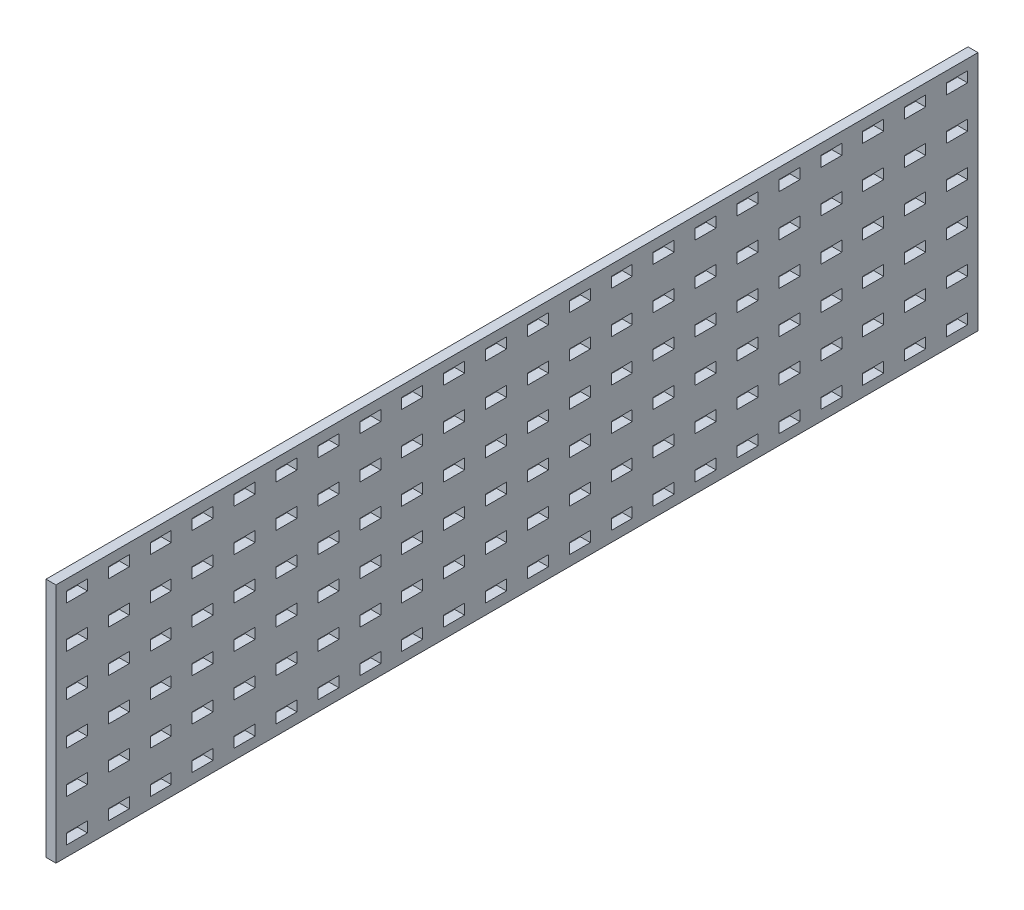
SolidWorks part; units mm, degrees
ref_plane "Front Plane" through (0, 0, 0) normal (0, 0, 1) x (1, 0, 0)
ref_plane "Top Plane" through (0, 0, 0) normal (0, 1, 0) x (1, 0, 0)
ref_plane "Right Plane" through (0, 0, 0) normal (1, 0, 0) x (0, 0, -1)
sketch "Sketch1" plane through (0, 0, 0) normal (1, 0, 0) x (0, 0, -1)
  line L1 (-279.4, -73.025) -> (279.4, -73.025)
  line L2 (-279.4, -73.025) -> (-279.4, 73.025)
  line L3 (-279.4, 73.025) -> (279.4, 73.025)
  line L4 (279.4, -73.025) -> (279.4, 73.025)
  line L5 (-279.4, -73.025) -> (279.4, 73.025) construction
  line L6 (-279.4, 73.025) -> (279.4, -73.025) construction
  point P0 (0, 0)
  dimension "D1" = 558.8
  dimension "D2" = 146.05
extrude "Boss-Extrude1" add sketch "Sketch1" along normal mid plane 6.0452
sketch "Sketch2" plane through (3.0226, 0, 0) normal (1, 0, 0) x (0, 0, -1)
  line L0 (-279.4, -73.025) -> (279.4, -73.025) construction
  line L1 (260.35, -60.325) -> (273.05, -60.325)
  line L2 (260.35, -60.325) -> (260.35, -66.675)
  line L3 (260.35, -66.675) -> (273.05, -66.675)
  line L4 (273.05, -60.325) -> (273.05, -66.675)
  line L5 (260.35, -60.325) -> (273.05, -66.675) construction
  line L6 (260.35, -66.675) -> (273.05, -60.325) construction
  line L7 (279.4, -73.025) -> (279.4, 73.025) construction
  line L8 (234.95, -66.675) -> (247.65, -66.675)
  line L9 (234.95, -60.325) -> (234.95, -66.675)
  line L10 (234.95, -60.325) -> (247.65, -60.325)
  line L11 (247.65, -60.325) -> (247.65, -66.675)
  line L12 (209.55, -66.675) -> (222.25, -66.675)
  line L13 (209.55, -60.325) -> (209.55, -66.675)
  line L14 (209.55, -60.325) -> (222.25, -60.325)
  line L15 (222.25, -60.325) -> (222.25, -66.675)
  line L16 (184.15, -66.675) -> (196.85, -66.675)
  line L17 (184.15, -60.325) -> (184.15, -66.675)
  line L18 (184.15, -60.325) -> (196.85, -60.325)
  line L19 (196.85, -60.325) -> (196.85, -66.675)
  line L20 (158.75, -66.675) -> (171.45, -66.675)
  line L21 (158.75, -60.325) -> (158.75, -66.675)
  line L22 (158.75, -60.325) -> (171.45, -60.325)
  line L23 (171.45, -60.325) -> (171.45, -66.675)
  line L24 (133.35, -66.675) -> (146.05, -66.675)
  line L25 (133.35, -60.325) -> (133.35, -66.675)
  line L26 (133.35, -60.325) -> (146.05, -60.325)
  line L27 (146.05, -60.325) -> (146.05, -66.675)
  line L28 (107.95, -66.675) -> (120.65, -66.675)
  line L29 (107.95, -60.325) -> (107.95, -66.675)
  line L30 (107.95, -60.325) -> (120.65, -60.325)
  line L31 (120.65, -60.325) -> (120.65, -66.675)
  line L32 (82.55, -66.675) -> (95.25, -66.675)
  line L33 (82.55, -60.325) -> (82.55, -66.675)
  line L34 (82.55, -60.325) -> (95.25, -60.325)
  line L35 (95.25, -60.325) -> (95.25, -66.675)
  line L36 (57.15, -66.675) -> (69.85, -66.675)
  line L37 (57.15, -60.325) -> (57.15, -66.675)
  line L38 (57.15, -60.325) -> (69.85, -60.325)
  line L39 (69.85, -60.325) -> (69.85, -66.675)
  line L40 (31.75, -66.675) -> (44.45, -66.675)
  line L41 (31.75, -60.325) -> (31.75, -66.675)
  line L42 (31.75, -60.325) -> (44.45, -60.325)
  line L43 (44.45, -60.325) -> (44.45, -66.675)
  line L44 (6.35, -66.675) -> (19.05, -66.675)
  line L45 (6.35, -60.325) -> (6.35, -66.675)
  line L46 (6.35, -60.325) -> (19.05, -60.325)
  line L47 (19.05, -60.325) -> (19.05, -66.675)
  line L48 (-19.05, -66.675) -> (-6.35, -66.675)
  line L49 (-19.05, -60.325) -> (-19.05, -66.675)
  line L50 (-19.05, -60.325) -> (-6.35, -60.325)
  line L51 (-6.35, -60.325) -> (-6.35, -66.675)
  line L52 (-44.45, -66.675) -> (-31.75, -66.675)
  line L53 (-44.45, -60.325) -> (-44.45, -66.675)
  line L54 (-44.45, -60.325) -> (-31.75, -60.325)
  line L55 (-31.75, -60.325) -> (-31.75, -66.675)
  line L56 (-69.85, -66.675) -> (-57.15, -66.675)
  line L57 (-69.85, -60.325) -> (-69.85, -66.675)
  line L58 (-69.85, -60.325) -> (-57.15, -60.325)
  line L59 (-57.15, -60.325) -> (-57.15, -66.675)
  line L60 (-95.25, -66.675) -> (-82.55, -66.675)
  line L61 (-95.25, -60.325) -> (-95.25, -66.675)
  line L62 (-95.25, -60.325) -> (-82.55, -60.325)
  line L63 (-82.55, -60.325) -> (-82.55, -66.675)
  line L64 (-120.65, -66.675) -> (-107.95, -66.675)
  line L65 (-120.65, -60.325) -> (-120.65, -66.675)
  line L66 (-120.65, -60.325) -> (-107.95, -60.325)
  line L67 (-107.95, -60.325) -> (-107.95, -66.675)
  line L68 (-146.05, -66.675) -> (-133.35, -66.675)
  line L69 (-146.05, -60.325) -> (-146.05, -66.675)
  line L70 (-146.05, -60.325) -> (-133.35, -60.325)
  line L71 (-133.35, -60.325) -> (-133.35, -66.675)
  line L72 (-171.45, -66.675) -> (-158.75, -66.675)
  line L73 (-171.45, -60.325) -> (-171.45, -66.675)
  line L74 (-171.45, -60.325) -> (-158.75, -60.325)
  line L75 (-158.75, -60.325) -> (-158.75, -66.675)
  line L76 (-196.85, -66.675) -> (-184.15, -66.675)
  line L77 (-196.85, -60.325) -> (-196.85, -66.675)
  line L78 (-196.85, -60.325) -> (-184.15, -60.325)
  line L79 (-184.15, -60.325) -> (-184.15, -66.675)
  line L80 (-222.25, -66.675) -> (-209.55, -66.675)
  line L81 (-222.25, -60.325) -> (-222.25, -66.675)
  line L82 (-222.25, -60.325) -> (-209.55, -60.325)
  line L83 (-209.55, -60.325) -> (-209.55, -66.675)
  line L84 (-247.65, -66.675) -> (-234.95, -66.675)
  line L85 (-247.65, -60.325) -> (-247.65, -66.675)
  line L86 (-247.65, -60.325) -> (-234.95, -60.325)
  line L87 (-234.95, -60.325) -> (-234.95, -66.675)
  line L88 (-273.05, -66.675) -> (-260.35, -66.675)
  line L89 (-273.05, -60.325) -> (-273.05, -66.675)
  line L90 (-273.05, -60.325) -> (-260.35, -60.325)
  line L91 (-260.35, -60.325) -> (-260.35, -66.675)
  line L92 (234.95, -41.275) -> (247.65, -41.275)
  line L93 (234.95, -34.925) -> (234.95, -41.275)
  line L94 (234.95, -34.925) -> (247.65, -34.925)
  line L95 (247.65, -34.925) -> (247.65, -41.275)
  line L96 (209.55, -41.275) -> (222.25, -41.275)
  line L97 (209.55, -34.925) -> (209.55, -41.275)
  line L98 (209.55, -34.925) -> (222.25, -34.925)
  line L99 (222.25, -34.925) -> (222.25, -41.275)
  line L100 (184.15, -41.275) -> (196.85, -41.275)
  line L101 (184.15, -34.925) -> (184.15, -41.275)
  line L102 (184.15, -34.925) -> (196.85, -34.925)
  line L103 (196.85, -34.925) -> (196.85, -41.275)
  line L104 (158.75, -41.275) -> (171.45, -41.275)
  line L105 (158.75, -34.925) -> (158.75, -41.275)
  line L106 (158.75, -34.925) -> (171.45, -34.925)
  line L107 (171.45, -34.925) -> (171.45, -41.275)
  line L108 (133.35, -41.275) -> (146.05, -41.275)
  line L109 (133.35, -34.925) -> (133.35, -41.275)
  line L110 (133.35, -34.925) -> (146.05, -34.925)
  line L111 (146.05, -34.925) -> (146.05, -41.275)
  line L112 (107.95, -41.275) -> (120.65, -41.275)
  line L113 (107.95, -34.925) -> (107.95, -41.275)
  line L114 (107.95, -34.925) -> (120.65, -34.925)
  line L115 (120.65, -34.925) -> (120.65, -41.275)
  line L116 (82.55, -41.275) -> (95.25, -41.275)
  line L117 (82.55, -34.925) -> (82.55, -41.275)
  line L118 (82.55, -34.925) -> (95.25, -34.925)
  line L119 (95.25, -34.925) -> (95.25, -41.275)
  line L120 (57.15, -41.275) -> (69.85, -41.275)
  line L121 (57.15, -34.925) -> (57.15, -41.275)
  line L122 (57.15, -34.925) -> (69.85, -34.925)
  line L123 (69.85, -34.925) -> (69.85, -41.275)
  line L124 (31.75, -41.275) -> (44.45, -41.275)
  line L125 (31.75, -34.925) -> (31.75, -41.275)
  line L126 (31.75, -34.925) -> (44.45, -34.925)
  line L127 (44.45, -34.925) -> (44.45, -41.275)
  line L128 (6.35, -41.275) -> (19.05, -41.275)
  line L129 (6.35, -34.925) -> (6.35, -41.275)
  line L130 (6.35, -34.925) -> (19.05, -34.925)
  line L131 (19.05, -34.925) -> (19.05, -41.275)
  line L132 (-19.05, -41.275) -> (-6.35, -41.275)
  line L133 (-19.05, -34.925) -> (-19.05, -41.275)
  line L134 (-19.05, -34.925) -> (-6.35, -34.925)
  line L135 (-6.35, -34.925) -> (-6.35, -41.275)
  line L136 (-44.45, -41.275) -> (-31.75, -41.275)
  line L137 (-44.45, -34.925) -> (-44.45, -41.275)
  line L138 (-44.45, -34.925) -> (-31.75, -34.925)
  line L139 (-31.75, -34.925) -> (-31.75, -41.275)
  line L140 (-69.85, -41.275) -> (-57.15, -41.275)
  line L141 (-69.85, -34.925) -> (-69.85, -41.275)
  line L142 (-69.85, -34.925) -> (-57.15, -34.925)
  line L143 (-57.15, -34.925) -> (-57.15, -41.275)
  line L144 (-95.25, -41.275) -> (-82.55, -41.275)
  line L145 (-95.25, -34.925) -> (-95.25, -41.275)
  line L146 (-95.25, -34.925) -> (-82.55, -34.925)
  line L147 (-82.55, -34.925) -> (-82.55, -41.275)
  line L148 (-120.65, -41.275) -> (-107.95, -41.275)
  line L149 (-120.65, -34.925) -> (-120.65, -41.275)
  line L150 (-120.65, -34.925) -> (-107.95, -34.925)
  line L151 (-107.95, -34.925) -> (-107.95, -41.275)
  line L152 (-146.05, -41.275) -> (-133.35, -41.275)
  line L153 (-146.05, -34.925) -> (-146.05, -41.275)
  line L154 (-146.05, -34.925) -> (-133.35, -34.925)
  line L155 (-133.35, -34.925) -> (-133.35, -41.275)
  line L156 (-171.45, -41.275) -> (-158.75, -41.275)
  line L157 (-171.45, -34.925) -> (-171.45, -41.275)
  line L158 (-171.45, -34.925) -> (-158.75, -34.925)
  line L159 (-158.75, -34.925) -> (-158.75, -41.275)
  line L160 (-196.85, -41.275) -> (-184.15, -41.275)
  line L161 (-196.85, -34.925) -> (-196.85, -41.275)
  line L162 (-196.85, -34.925) -> (-184.15, -34.925)
  line L163 (-184.15, -34.925) -> (-184.15, -41.275)
  line L164 (-222.25, -41.275) -> (-209.55, -41.275)
  line L165 (-222.25, -34.925) -> (-222.25, -41.275)
  line L166 (-222.25, -34.925) -> (-209.55, -34.925)
  line L167 (-209.55, -34.925) -> (-209.55, -41.275)
  line L168 (-247.65, -41.275) -> (-234.95, -41.275)
  line L169 (-247.65, -34.925) -> (-247.65, -41.275)
  line L170 (-247.65, -34.925) -> (-234.95, -34.925)
  line L171 (-234.95, -34.925) -> (-234.95, -41.275)
  line L172 (-273.05, -41.275) -> (-260.35, -41.275)
  line L173 (-273.05, -34.925) -> (-273.05, -41.275)
  line L174 (-273.05, -34.925) -> (-260.35, -34.925)
  line L175 (-260.35, -34.925) -> (-260.35, -41.275)
  line L176 (234.95, -15.875) -> (247.65, -15.875)
  line L177 (234.95, -9.525) -> (234.95, -15.875)
  line L178 (234.95, -9.525) -> (247.65, -9.525)
  line L179 (247.65, -9.525) -> (247.65, -15.875)
  line L180 (209.55, -15.875) -> (222.25, -15.875)
  line L181 (209.55, -9.525) -> (209.55, -15.875)
  line L182 (209.55, -9.525) -> (222.25, -9.525)
  line L183 (222.25, -9.525) -> (222.25, -15.875)
  line L184 (184.15, -15.875) -> (196.85, -15.875)
  line L185 (184.15, -9.525) -> (184.15, -15.875)
  line L186 (184.15, -9.525) -> (196.85, -9.525)
  line L187 (196.85, -9.525) -> (196.85, -15.875)
  line L188 (158.75, -15.875) -> (171.45, -15.875)
  line L189 (158.75, -9.525) -> (158.75, -15.875)
  line L190 (158.75, -9.525) -> (171.45, -9.525)
  line L191 (171.45, -9.525) -> (171.45, -15.875)
  line L192 (133.35, -15.875) -> (146.05, -15.875)
  line L193 (133.35, -9.525) -> (133.35, -15.875)
  line L194 (133.35, -9.525) -> (146.05, -9.525)
  line L195 (146.05, -9.525) -> (146.05, -15.875)
  line L196 (107.95, -15.875) -> (120.65, -15.875)
  line L197 (107.95, -9.525) -> (107.95, -15.875)
  line L198 (107.95, -9.525) -> (120.65, -9.525)
  line L199 (120.65, -9.525) -> (120.65, -15.875)
  line L200 (82.55, -15.875) -> (95.25, -15.875)
  line L201 (82.55, -9.525) -> (82.55, -15.875)
  line L202 (82.55, -9.525) -> (95.25, -9.525)
  line L203 (95.25, -9.525) -> (95.25, -15.875)
  line L204 (57.15, -15.875) -> (69.85, -15.875)
  line L205 (57.15, -9.525) -> (57.15, -15.875)
  line L206 (57.15, -9.525) -> (69.85, -9.525)
  line L207 (69.85, -9.525) -> (69.85, -15.875)
  line L208 (31.75, -15.875) -> (44.45, -15.875)
  line L209 (31.75, -9.525) -> (31.75, -15.875)
  line L210 (31.75, -9.525) -> (44.45, -9.525)
  line L211 (44.45, -9.525) -> (44.45, -15.875)
  line L212 (6.35, -15.875) -> (19.05, -15.875)
  line L213 (6.35, -9.525) -> (6.35, -15.875)
  line L214 (6.35, -9.525) -> (19.05, -9.525)
  line L215 (19.05, -9.525) -> (19.05, -15.875)
  line L216 (-19.05, -15.875) -> (-6.35, -15.875)
  line L217 (-19.05, -9.525) -> (-19.05, -15.875)
  line L218 (-19.05, -9.525) -> (-6.35, -9.525)
  line L219 (-6.35, -9.525) -> (-6.35, -15.875)
  line L220 (-44.45, -15.875) -> (-31.75, -15.875)
  line L221 (-44.45, -9.525) -> (-44.45, -15.875)
  line L222 (-44.45, -9.525) -> (-31.75, -9.525)
  line L223 (-31.75, -9.525) -> (-31.75, -15.875)
  line L224 (-69.85, -15.875) -> (-57.15, -15.875)
  line L225 (-69.85, -9.525) -> (-69.85, -15.875)
  line L226 (-69.85, -9.525) -> (-57.15, -9.525)
  line L227 (-57.15, -9.525) -> (-57.15, -15.875)
  line L228 (-95.25, -15.875) -> (-82.55, -15.875)
  line L229 (-95.25, -9.525) -> (-95.25, -15.875)
  line L230 (-95.25, -9.525) -> (-82.55, -9.525)
  line L231 (-82.55, -9.525) -> (-82.55, -15.875)
  line L232 (-120.65, -15.875) -> (-107.95, -15.875)
  line L233 (-120.65, -9.525) -> (-120.65, -15.875)
  line L234 (-120.65, -9.525) -> (-107.95, -9.525)
  line L235 (-107.95, -9.525) -> (-107.95, -15.875)
  line L236 (-146.05, -15.875) -> (-133.35, -15.875)
  line L237 (-146.05, -9.525) -> (-146.05, -15.875)
  line L238 (-146.05, -9.525) -> (-133.35, -9.525)
  line L239 (-133.35, -9.525) -> (-133.35, -15.875)
  line L240 (-171.45, -15.875) -> (-158.75, -15.875)
  line L241 (-171.45, -9.525) -> (-171.45, -15.875)
  line L242 (-171.45, -9.525) -> (-158.75, -9.525)
  line L243 (-158.75, -9.525) -> (-158.75, -15.875)
  line L244 (-196.85, -15.875) -> (-184.15, -15.875)
  line L245 (-196.85, -9.525) -> (-196.85, -15.875)
  line L246 (-196.85, -9.525) -> (-184.15, -9.525)
  line L247 (-184.15, -9.525) -> (-184.15, -15.875)
  line L248 (-222.25, -15.875) -> (-209.55, -15.875)
  line L249 (-222.25, -9.525) -> (-222.25, -15.875)
  line L250 (-222.25, -9.525) -> (-209.55, -9.525)
  line L251 (-209.55, -9.525) -> (-209.55, -15.875)
  line L252 (-247.65, -15.875) -> (-234.95, -15.875)
  line L253 (-247.65, -9.525) -> (-247.65, -15.875)
  line L254 (-247.65, -9.525) -> (-234.95, -9.525)
  line L255 (-234.95, -9.525) -> (-234.95, -15.875)
  line L256 (-273.05, -15.875) -> (-260.35, -15.875)
  line L257 (-273.05, -9.525) -> (-273.05, -15.875)
  line L258 (-273.05, -9.525) -> (-260.35, -9.525)
  line L259 (-260.35, -9.525) -> (-260.35, -15.875)
  line L260 (234.95, 9.525) -> (247.65, 9.525)
  line L261 (234.95, 15.875) -> (234.95, 9.525)
  line L262 (234.95, 15.875) -> (247.65, 15.875)
  line L263 (247.65, 15.875) -> (247.65, 9.525)
  line L264 (209.55, 9.525) -> (222.25, 9.525)
  line L265 (209.55, 15.875) -> (209.55, 9.525)
  line L266 (209.55, 15.875) -> (222.25, 15.875)
  line L267 (222.25, 15.875) -> (222.25, 9.525)
  line L268 (184.15, 9.525) -> (196.85, 9.525)
  line L269 (184.15, 15.875) -> (184.15, 9.525)
  line L270 (184.15, 15.875) -> (196.85, 15.875)
  line L271 (196.85, 15.875) -> (196.85, 9.525)
  line L272 (158.75, 9.525) -> (171.45, 9.525)
  line L273 (158.75, 15.875) -> (158.75, 9.525)
  line L274 (158.75, 15.875) -> (171.45, 15.875)
  line L275 (171.45, 15.875) -> (171.45, 9.525)
  line L276 (133.35, 9.525) -> (146.05, 9.525)
  line L277 (133.35, 15.875) -> (133.35, 9.525)
  line L278 (133.35, 15.875) -> (146.05, 15.875)
  line L279 (146.05, 15.875) -> (146.05, 9.525)
  line L280 (107.95, 9.525) -> (120.65, 9.525)
  line L281 (107.95, 15.875) -> (107.95, 9.525)
  line L282 (107.95, 15.875) -> (120.65, 15.875)
  line L283 (120.65, 15.875) -> (120.65, 9.525)
  line L284 (82.55, 9.525) -> (95.25, 9.525)
  line L285 (82.55, 15.875) -> (82.55, 9.525)
  line L286 (82.55, 15.875) -> (95.25, 15.875)
  line L287 (95.25, 15.875) -> (95.25, 9.525)
  line L288 (57.15, 9.525) -> (69.85, 9.525)
  line L289 (57.15, 15.875) -> (57.15, 9.525)
  line L290 (57.15, 15.875) -> (69.85, 15.875)
  line L291 (69.85, 15.875) -> (69.85, 9.525)
  line L292 (31.75, 9.525) -> (44.45, 9.525)
  line L293 (31.75, 15.875) -> (31.75, 9.525)
  line L294 (31.75, 15.875) -> (44.45, 15.875)
  line L295 (44.45, 15.875) -> (44.45, 9.525)
  line L296 (6.35, 9.525) -> (19.05, 9.525)
  line L297 (6.35, 15.875) -> (6.35, 9.525)
  line L298 (6.35, 15.875) -> (19.05, 15.875)
  line L299 (19.05, 15.875) -> (19.05, 9.525)
  line L300 (-19.05, 9.525) -> (-6.35, 9.525)
  line L301 (-19.05, 15.875) -> (-19.05, 9.525)
  line L302 (-19.05, 15.875) -> (-6.35, 15.875)
  line L303 (-6.35, 15.875) -> (-6.35, 9.525)
  line L304 (-44.45, 9.525) -> (-31.75, 9.525)
  line L305 (-44.45, 15.875) -> (-44.45, 9.525)
  line L306 (-44.45, 15.875) -> (-31.75, 15.875)
  line L307 (-31.75, 15.875) -> (-31.75, 9.525)
  line L308 (-69.85, 9.525) -> (-57.15, 9.525)
  line L309 (-69.85, 15.875) -> (-69.85, 9.525)
  line L310 (-69.85, 15.875) -> (-57.15, 15.875)
  line L311 (-57.15, 15.875) -> (-57.15, 9.525)
  line L312 (-95.25, 9.525) -> (-82.55, 9.525)
  line L313 (-95.25, 15.875) -> (-95.25, 9.525)
  line L314 (-95.25, 15.875) -> (-82.55, 15.875)
  line L315 (-82.55, 15.875) -> (-82.55, 9.525)
  line L316 (-120.65, 9.525) -> (-107.95, 9.525)
  line L317 (-120.65, 15.875) -> (-120.65, 9.525)
  line L318 (-120.65, 15.875) -> (-107.95, 15.875)
  line L319 (-107.95, 15.875) -> (-107.95, 9.525)
  line L320 (-146.05, 9.525) -> (-133.35, 9.525)
  line L321 (-146.05, 15.875) -> (-146.05, 9.525)
  line L322 (-146.05, 15.875) -> (-133.35, 15.875)
  line L323 (-133.35, 15.875) -> (-133.35, 9.525)
  line L324 (-171.45, 9.525) -> (-158.75, 9.525)
  line L325 (-171.45, 15.875) -> (-171.45, 9.525)
  line L326 (-171.45, 15.875) -> (-158.75, 15.875)
  line L327 (-158.75, 15.875) -> (-158.75, 9.525)
  line L328 (-196.85, 9.525) -> (-184.15, 9.525)
  line L329 (-196.85, 15.875) -> (-196.85, 9.525)
  line L330 (-196.85, 15.875) -> (-184.15, 15.875)
  line L331 (-184.15, 15.875) -> (-184.15, 9.525)
  line L332 (-222.25, 9.525) -> (-209.55, 9.525)
  line L333 (-222.25, 15.875) -> (-222.25, 9.525)
  line L334 (-222.25, 15.875) -> (-209.55, 15.875)
  line L335 (-209.55, 15.875) -> (-209.55, 9.525)
  line L336 (-247.65, 9.525) -> (-234.95, 9.525)
  line L337 (-247.65, 15.875) -> (-247.65, 9.525)
  line L338 (-247.65, 15.875) -> (-234.95, 15.875)
  line L339 (-234.95, 15.875) -> (-234.95, 9.525)
  line L340 (-273.05, 9.525) -> (-260.35, 9.525)
  line L341 (-273.05, 15.875) -> (-273.05, 9.525)
  line L342 (-273.05, 15.875) -> (-260.35, 15.875)
  line L343 (-260.35, 15.875) -> (-260.35, 9.525)
  line L344 (234.95, 34.925) -> (247.65, 34.925)
  line L345 (234.95, 41.275) -> (234.95, 34.925)
  line L346 (234.95, 41.275) -> (247.65, 41.275)
  line L347 (247.65, 41.275) -> (247.65, 34.925)
  line L348 (209.55, 34.925) -> (222.25, 34.925)
  line L349 (209.55, 41.275) -> (209.55, 34.925)
  line L350 (209.55, 41.275) -> (222.25, 41.275)
  line L351 (222.25, 41.275) -> (222.25, 34.925)
  line L352 (184.15, 34.925) -> (196.85, 34.925)
  line L353 (184.15, 41.275) -> (184.15, 34.925)
  line L354 (184.15, 41.275) -> (196.85, 41.275)
  line L355 (196.85, 41.275) -> (196.85, 34.925)
  line L356 (158.75, 34.925) -> (171.45, 34.925)
  line L357 (158.75, 41.275) -> (158.75, 34.925)
  line L358 (158.75, 41.275) -> (171.45, 41.275)
  line L359 (171.45, 41.275) -> (171.45, 34.925)
  line L360 (133.35, 34.925) -> (146.05, 34.925)
  line L361 (133.35, 41.275) -> (133.35, 34.925)
  line L362 (133.35, 41.275) -> (146.05, 41.275)
  line L363 (146.05, 41.275) -> (146.05, 34.925)
  line L364 (107.95, 34.925) -> (120.65, 34.925)
  line L365 (107.95, 41.275) -> (107.95, 34.925)
  line L366 (107.95, 41.275) -> (120.65, 41.275)
  line L367 (120.65, 41.275) -> (120.65, 34.925)
  line L368 (82.55, 34.925) -> (95.25, 34.925)
  line L369 (82.55, 41.275) -> (82.55, 34.925)
  line L370 (82.55, 41.275) -> (95.25, 41.275)
  line L371 (95.25, 41.275) -> (95.25, 34.925)
  line L372 (57.15, 34.925) -> (69.85, 34.925)
  line L373 (57.15, 41.275) -> (57.15, 34.925)
  line L374 (57.15, 41.275) -> (69.85, 41.275)
  line L375 (69.85, 41.275) -> (69.85, 34.925)
  line L376 (31.75, 34.925) -> (44.45, 34.925)
  line L377 (31.75, 41.275) -> (31.75, 34.925)
  line L378 (31.75, 41.275) -> (44.45, 41.275)
  line L379 (44.45, 41.275) -> (44.45, 34.925)
  line L380 (6.35, 34.925) -> (19.05, 34.925)
  line L381 (6.35, 41.275) -> (6.35, 34.925)
  line L382 (6.35, 41.275) -> (19.05, 41.275)
  line L383 (19.05, 41.275) -> (19.05, 34.925)
  line L384 (-19.05, 34.925) -> (-6.35, 34.925)
  line L385 (-19.05, 41.275) -> (-19.05, 34.925)
  line L386 (-19.05, 41.275) -> (-6.35, 41.275)
  line L387 (-6.35, 41.275) -> (-6.35, 34.925)
  line L388 (-44.45, 34.925) -> (-31.75, 34.925)
  line L389 (-44.45, 41.275) -> (-44.45, 34.925)
  line L390 (-44.45, 41.275) -> (-31.75, 41.275)
  line L391 (-31.75, 41.275) -> (-31.75, 34.925)
  line L392 (-69.85, 34.925) -> (-57.15, 34.925)
  line L393 (-69.85, 41.275) -> (-69.85, 34.925)
  line L394 (-69.85, 41.275) -> (-57.15, 41.275)
  line L395 (-57.15, 41.275) -> (-57.15, 34.925)
  line L396 (-95.25, 34.925) -> (-82.55, 34.925)
  line L397 (-95.25, 41.275) -> (-95.25, 34.925)
  line L398 (-95.25, 41.275) -> (-82.55, 41.275)
  line L399 (-82.55, 41.275) -> (-82.55, 34.925)
  line L400 (-120.65, 34.925) -> (-107.95, 34.925)
  line L401 (-120.65, 41.275) -> (-120.65, 34.925)
  line L402 (-120.65, 41.275) -> (-107.95, 41.275)
  line L403 (-107.95, 41.275) -> (-107.95, 34.925)
  line L404 (-146.05, 34.925) -> (-133.35, 34.925)
  line L405 (-146.05, 41.275) -> (-146.05, 34.925)
  line L406 (-146.05, 41.275) -> (-133.35, 41.275)
  line L407 (-133.35, 41.275) -> (-133.35, 34.925)
  line L408 (-171.45, 34.925) -> (-158.75, 34.925)
  line L409 (-171.45, 41.275) -> (-171.45, 34.925)
  line L410 (-171.45, 41.275) -> (-158.75, 41.275)
  line L411 (-158.75, 41.275) -> (-158.75, 34.925)
  line L412 (-196.85, 34.925) -> (-184.15, 34.925)
  line L413 (-196.85, 41.275) -> (-196.85, 34.925)
  line L414 (-196.85, 41.275) -> (-184.15, 41.275)
  line L415 (-184.15, 41.275) -> (-184.15, 34.925)
  line L416 (-222.25, 34.925) -> (-209.55, 34.925)
  line L417 (-222.25, 41.275) -> (-222.25, 34.925)
  line L418 (-222.25, 41.275) -> (-209.55, 41.275)
  line L419 (-209.55, 41.275) -> (-209.55, 34.925)
  line L420 (-247.65, 34.925) -> (-234.95, 34.925)
  line L421 (-247.65, 41.275) -> (-247.65, 34.925)
  line L422 (-247.65, 41.275) -> (-234.95, 41.275)
  line L423 (-234.95, 41.275) -> (-234.95, 34.925)
  line L424 (-273.05, 34.925) -> (-260.35, 34.925)
  line L425 (-273.05, 41.275) -> (-273.05, 34.925)
  line L426 (-273.05, 41.275) -> (-260.35, 41.275)
  line L427 (-260.35, 41.275) -> (-260.35, 34.925)
  line L428 (234.95, 60.325) -> (247.65, 60.325)
  line L429 (234.95, 66.675) -> (234.95, 60.325)
  line L430 (234.95, 66.675) -> (247.65, 66.675)
  line L431 (247.65, 66.675) -> (247.65, 60.325)
  line L432 (209.55, 60.325) -> (222.25, 60.325)
  line L433 (209.55, 66.675) -> (209.55, 60.325)
  line L434 (209.55, 66.675) -> (222.25, 66.675)
  line L435 (222.25, 66.675) -> (222.25, 60.325)
  line L436 (184.15, 60.325) -> (196.85, 60.325)
  line L437 (184.15, 66.675) -> (184.15, 60.325)
  line L438 (184.15, 66.675) -> (196.85, 66.675)
  line L439 (196.85, 66.675) -> (196.85, 60.325)
  line L440 (158.75, 60.325) -> (171.45, 60.325)
  line L441 (158.75, 66.675) -> (158.75, 60.325)
  line L442 (158.75, 66.675) -> (171.45, 66.675)
  line L443 (171.45, 66.675) -> (171.45, 60.325)
  line L444 (133.35, 60.325) -> (146.05, 60.325)
  line L445 (133.35, 66.675) -> (133.35, 60.325)
  line L446 (133.35, 66.675) -> (146.05, 66.675)
  line L447 (146.05, 66.675) -> (146.05, 60.325)
  line L448 (107.95, 60.325) -> (120.65, 60.325)
  line L449 (107.95, 66.675) -> (107.95, 60.325)
  line L450 (107.95, 66.675) -> (120.65, 66.675)
  line L451 (120.65, 66.675) -> (120.65, 60.325)
  line L452 (82.55, 60.325) -> (95.25, 60.325)
  line L453 (82.55, 66.675) -> (82.55, 60.325)
  line L454 (82.55, 66.675) -> (95.25, 66.675)
  line L455 (95.25, 66.675) -> (95.25, 60.325)
  line L456 (57.15, 60.325) -> (69.85, 60.325)
  line L457 (57.15, 66.675) -> (57.15, 60.325)
  line L458 (57.15, 66.675) -> (69.85, 66.675)
  line L459 (69.85, 66.675) -> (69.85, 60.325)
  line L460 (31.75, 60.325) -> (44.45, 60.325)
  line L461 (31.75, 66.675) -> (31.75, 60.325)
  line L462 (31.75, 66.675) -> (44.45, 66.675)
  line L463 (44.45, 66.675) -> (44.45, 60.325)
  line L464 (6.35, 60.325) -> (19.05, 60.325)
  line L465 (6.35, 66.675) -> (6.35, 60.325)
  line L466 (6.35, 66.675) -> (19.05, 66.675)
  line L467 (19.05, 66.675) -> (19.05, 60.325)
  line L468 (-19.05, 60.325) -> (-6.35, 60.325)
  line L469 (-19.05, 66.675) -> (-19.05, 60.325)
  line L470 (-19.05, 66.675) -> (-6.35, 66.675)
  line L471 (-6.35, 66.675) -> (-6.35, 60.325)
  line L472 (-44.45, 60.325) -> (-31.75, 60.325)
  line L473 (-44.45, 66.675) -> (-44.45, 60.325)
  line L474 (-44.45, 66.675) -> (-31.75, 66.675)
  line L475 (-31.75, 66.675) -> (-31.75, 60.325)
  line L476 (-69.85, 60.325) -> (-57.15, 60.325)
  line L477 (-69.85, 66.675) -> (-69.85, 60.325)
  line L478 (-69.85, 66.675) -> (-57.15, 66.675)
  line L479 (-57.15, 66.675) -> (-57.15, 60.325)
  line L480 (-95.25, 60.325) -> (-82.55, 60.325)
  line L481 (-95.25, 66.675) -> (-95.25, 60.325)
  line L482 (-95.25, 66.675) -> (-82.55, 66.675)
  line L483 (-82.55, 66.675) -> (-82.55, 60.325)
  line L484 (-120.65, 60.325) -> (-107.95, 60.325)
  line L485 (-120.65, 66.675) -> (-120.65, 60.325)
  line L486 (-120.65, 66.675) -> (-107.95, 66.675)
  line L487 (-107.95, 66.675) -> (-107.95, 60.325)
  line L488 (-146.05, 60.325) -> (-133.35, 60.325)
  line L489 (-146.05, 66.675) -> (-146.05, 60.325)
  line L490 (-146.05, 66.675) -> (-133.35, 66.675)
  line L491 (-133.35, 66.675) -> (-133.35, 60.325)
  line L492 (-171.45, 60.325) -> (-158.75, 60.325)
  line L493 (-171.45, 66.675) -> (-171.45, 60.325)
  line L494 (-171.45, 66.675) -> (-158.75, 66.675)
  line L495 (-158.75, 66.675) -> (-158.75, 60.325)
  line L496 (-196.85, 60.325) -> (-184.15, 60.325)
  line L497 (-196.85, 66.675) -> (-196.85, 60.325)
  line L498 (-196.85, 66.675) -> (-184.15, 66.675)
  line L499 (-184.15, 66.675) -> (-184.15, 60.325)
  line L500 (-222.25, 60.325) -> (-209.55, 60.325)
  line L501 (-222.25, 66.675) -> (-222.25, 60.325)
  line L502 (-222.25, 66.675) -> (-209.55, 66.675)
  line L503 (-209.55, 66.675) -> (-209.55, 60.325)
  line L504 (-247.65, 60.325) -> (-234.95, 60.325)
  line L505 (-247.65, 66.675) -> (-247.65, 60.325)
  line L506 (-247.65, 66.675) -> (-234.95, 66.675)
  line L507 (-234.95, 66.675) -> (-234.95, 60.325)
  line L508 (-273.05, 60.325) -> (-260.35, 60.325)
  line L509 (-273.05, 66.675) -> (-273.05, 60.325)
  line L510 (-273.05, 66.675) -> (-260.35, 66.675)
  line L511 (-260.35, 66.675) -> (-260.35, 60.325)
  line L512 (234.95, 85.725) -> (247.65, 85.725)
  line L513 (234.95, 92.075) -> (234.95, 85.725)
  line L514 (234.95, 92.075) -> (247.65, 92.075)
  line L515 (247.65, 92.075) -> (247.65, 85.725)
  line L516 (209.55, 85.725) -> (222.25, 85.725)
  line L517 (209.55, 92.075) -> (209.55, 85.725)
  line L518 (209.55, 92.075) -> (222.25, 92.075)
  line L519 (222.25, 92.075) -> (222.25, 85.725)
  line L520 (184.15, 85.725) -> (196.85, 85.725)
  line L521 (184.15, 92.075) -> (184.15, 85.725)
  line L522 (184.15, 92.075) -> (196.85, 92.075)
  line L523 (196.85, 92.075) -> (196.85, 85.725)
  line L524 (158.75, 85.725) -> (171.45, 85.725)
  line L525 (158.75, 92.075) -> (158.75, 85.725)
  line L526 (158.75, 92.075) -> (171.45, 92.075)
  line L527 (171.45, 92.075) -> (171.45, 85.725)
  line L528 (133.35, 85.725) -> (146.05, 85.725)
  line L529 (133.35, 92.075) -> (133.35, 85.725)
  line L530 (133.35, 92.075) -> (146.05, 92.075)
  line L531 (146.05, 92.075) -> (146.05, 85.725)
  line L532 (107.95, 85.725) -> (120.65, 85.725)
  line L533 (107.95, 92.075) -> (107.95, 85.725)
  line L534 (107.95, 92.075) -> (120.65, 92.075)
  line L535 (120.65, 92.075) -> (120.65, 85.725)
  line L536 (82.55, 85.725) -> (95.25, 85.725)
  line L537 (82.55, 92.075) -> (82.55, 85.725)
  line L538 (82.55, 92.075) -> (95.25, 92.075)
  line L539 (95.25, 92.075) -> (95.25, 85.725)
  line L540 (57.15, 85.725) -> (69.85, 85.725)
  line L541 (57.15, 92.075) -> (57.15, 85.725)
  line L542 (57.15, 92.075) -> (69.85, 92.075)
  line L543 (69.85, 92.075) -> (69.85, 85.725)
  line L544 (31.75, 85.725) -> (44.45, 85.725)
  line L545 (31.75, 92.075) -> (31.75, 85.725)
  line L546 (31.75, 92.075) -> (44.45, 92.075)
  line L547 (44.45, 92.075) -> (44.45, 85.725)
  line L548 (6.35, 85.725) -> (19.05, 85.725)
  line L549 (6.35, 92.075) -> (6.35, 85.725)
  line L550 (6.35, 92.075) -> (19.05, 92.075)
  line L551 (19.05, 92.075) -> (19.05, 85.725)
  line L552 (-19.05, 85.725) -> (-6.35, 85.725)
  line L553 (-19.05, 92.075) -> (-19.05, 85.725)
  line L554 (-19.05, 92.075) -> (-6.35, 92.075)
  line L555 (-6.35, 92.075) -> (-6.35, 85.725)
  line L556 (-44.45, 85.725) -> (-31.75, 85.725)
  line L557 (-44.45, 92.075) -> (-44.45, 85.725)
  line L558 (-44.45, 92.075) -> (-31.75, 92.075)
  line L559 (-31.75, 92.075) -> (-31.75, 85.725)
  line L560 (-69.85, 85.725) -> (-57.15, 85.725)
  line L561 (-69.85, 92.075) -> (-69.85, 85.725)
  line L562 (-69.85, 92.075) -> (-57.15, 92.075)
  line L563 (-57.15, 92.075) -> (-57.15, 85.725)
  line L564 (-95.25, 85.725) -> (-82.55, 85.725)
  line L565 (-95.25, 92.075) -> (-95.25, 85.725)
  line L566 (-95.25, 92.075) -> (-82.55, 92.075)
  line L567 (-82.55, 92.075) -> (-82.55, 85.725)
  line L568 (-120.65, 85.725) -> (-107.95, 85.725)
  line L569 (-120.65, 92.075) -> (-120.65, 85.725)
  line L570 (-120.65, 92.075) -> (-107.95, 92.075)
  line L571 (-107.95, 92.075) -> (-107.95, 85.725)
  line L572 (-146.05, 85.725) -> (-133.35, 85.725)
  line L573 (-146.05, 92.075) -> (-146.05, 85.725)
  line L574 (-146.05, 92.075) -> (-133.35, 92.075)
  line L575 (-133.35, 92.075) -> (-133.35, 85.725)
  line L576 (-171.45, 85.725) -> (-158.75, 85.725)
  line L577 (-171.45, 92.075) -> (-171.45, 85.725)
  line L578 (-171.45, 92.075) -> (-158.75, 92.075)
  line L579 (-158.75, 92.075) -> (-158.75, 85.725)
  line L580 (-196.85, 85.725) -> (-184.15, 85.725)
  line L581 (-196.85, 92.075) -> (-196.85, 85.725)
  line L582 (-196.85, 92.075) -> (-184.15, 92.075)
  line L583 (-184.15, 92.075) -> (-184.15, 85.725)
  line L584 (-222.25, 85.725) -> (-209.55, 85.725)
  line L585 (-222.25, 92.075) -> (-222.25, 85.725)
  line L586 (-222.25, 92.075) -> (-209.55, 92.075)
  line L587 (-209.55, 92.075) -> (-209.55, 85.725)
  line L588 (-247.65, 85.725) -> (-234.95, 85.725)
  line L589 (-247.65, 92.075) -> (-247.65, 85.725)
  line L590 (-247.65, 92.075) -> (-234.95, 92.075)
  line L591 (-234.95, 92.075) -> (-234.95, 85.725)
  line L592 (-273.05, 85.725) -> (-260.35, 85.725)
  line L593 (-273.05, 92.075) -> (-273.05, 85.725)
  line L594 (-273.05, 92.075) -> (-260.35, 92.075)
  line L595 (-260.35, 92.075) -> (-260.35, 85.725)
  line L596 (234.95, 111.125) -> (247.65, 111.125)
  line L597 (234.95, 117.475) -> (234.95, 111.125)
  line L598 (234.95, 117.475) -> (247.65, 117.475)
  line L599 (247.65, 117.475) -> (247.65, 111.125)
  line L600 (209.55, 111.125) -> (222.25, 111.125)
  line L601 (209.55, 117.475) -> (209.55, 111.125)
  line L602 (209.55, 117.475) -> (222.25, 117.475)
  line L603 (222.25, 117.475) -> (222.25, 111.125)
  line L604 (184.15, 111.125) -> (196.85, 111.125)
  line L605 (184.15, 117.475) -> (184.15, 111.125)
  line L606 (184.15, 117.475) -> (196.85, 117.475)
  line L607 (196.85, 117.475) -> (196.85, 111.125)
  line L608 (158.75, 111.125) -> (171.45, 111.125)
  line L609 (158.75, 117.475) -> (158.75, 111.125)
  line L610 (158.75, 117.475) -> (171.45, 117.475)
  line L611 (171.45, 117.475) -> (171.45, 111.125)
  line L612 (133.35, 111.125) -> (146.05, 111.125)
  line L613 (133.35, 117.475) -> (133.35, 111.125)
  line L614 (133.35, 117.475) -> (146.05, 117.475)
  line L615 (146.05, 117.475) -> (146.05, 111.125)
  line L616 (107.95, 111.125) -> (120.65, 111.125)
  line L617 (107.95, 117.475) -> (107.95, 111.125)
  line L618 (107.95, 117.475) -> (120.65, 117.475)
  line L619 (120.65, 117.475) -> (120.65, 111.125)
  line L620 (82.55, 111.125) -> (95.25, 111.125)
  line L621 (82.55, 117.475) -> (82.55, 111.125)
  line L622 (82.55, 117.475) -> (95.25, 117.475)
  line L623 (95.25, 117.475) -> (95.25, 111.125)
  line L624 (57.15, 111.125) -> (69.85, 111.125)
  line L625 (57.15, 117.475) -> (57.15, 111.125)
  line L626 (57.15, 117.475) -> (69.85, 117.475)
  line L627 (69.85, 117.475) -> (69.85, 111.125)
  line L628 (31.75, 111.125) -> (44.45, 111.125)
  line L629 (31.75, 117.475) -> (31.75, 111.125)
  line L630 (31.75, 117.475) -> (44.45, 117.475)
  line L631 (44.45, 117.475) -> (44.45, 111.125)
  line L632 (6.35, 111.125) -> (19.05, 111.125)
  line L633 (6.35, 117.475) -> (6.35, 111.125)
  line L634 (6.35, 117.475) -> (19.05, 117.475)
  line L635 (19.05, 117.475) -> (19.05, 111.125)
  line L636 (-19.05, 111.125) -> (-6.35, 111.125)
  line L637 (-19.05, 117.475) -> (-19.05, 111.125)
  line L638 (-19.05, 117.475) -> (-6.35, 117.475)
  line L639 (-6.35, 117.475) -> (-6.35, 111.125)
  line L640 (-44.45, 111.125) -> (-31.75, 111.125)
  line L641 (-44.45, 117.475) -> (-44.45, 111.125)
  line L642 (-44.45, 117.475) -> (-31.75, 117.475)
  line L643 (-31.75, 117.475) -> (-31.75, 111.125)
  line L644 (-69.85, 111.125) -> (-57.15, 111.125)
  line L645 (-69.85, 117.475) -> (-69.85, 111.125)
  line L646 (-69.85, 117.475) -> (-57.15, 117.475)
  line L647 (-57.15, 117.475) -> (-57.15, 111.125)
  line L648 (-95.25, 111.125) -> (-82.55, 111.125)
  line L649 (-95.25, 117.475) -> (-95.25, 111.125)
  line L650 (-95.25, 117.475) -> (-82.55, 117.475)
  line L651 (-82.55, 117.475) -> (-82.55, 111.125)
  line L652 (-120.65, 111.125) -> (-107.95, 111.125)
  line L653 (-120.65, 117.475) -> (-120.65, 111.125)
  line L654 (-120.65, 117.475) -> (-107.95, 117.475)
  line L655 (-107.95, 117.475) -> (-107.95, 111.125)
  line L656 (-146.05, 111.125) -> (-133.35, 111.125)
  line L657 (-146.05, 117.475) -> (-146.05, 111.125)
  line L658 (-146.05, 117.475) -> (-133.35, 117.475)
  line L659 (-133.35, 117.475) -> (-133.35, 111.125)
  line L660 (-171.45, 111.125) -> (-158.75, 111.125)
  line L661 (-171.45, 117.475) -> (-171.45, 111.125)
  line L662 (-171.45, 117.475) -> (-158.75, 117.475)
  line L663 (-158.75, 117.475) -> (-158.75, 111.125)
  line L664 (-196.85, 111.125) -> (-184.15, 111.125)
  line L665 (-196.85, 117.475) -> (-196.85, 111.125)
  line L666 (-196.85, 117.475) -> (-184.15, 117.475)
  line L667 (-184.15, 117.475) -> (-184.15, 111.125)
  line L668 (-222.25, 111.125) -> (-209.55, 111.125)
  line L669 (-222.25, 117.475) -> (-222.25, 111.125)
  line L670 (-222.25, 117.475) -> (-209.55, 117.475)
  line L671 (-209.55, 117.475) -> (-209.55, 111.125)
  line L672 (-247.65, 111.125) -> (-234.95, 111.125)
  line L673 (-247.65, 117.475) -> (-247.65, 111.125)
  line L674 (-247.65, 117.475) -> (-234.95, 117.475)
  line L675 (-234.95, 117.475) -> (-234.95, 111.125)
  line L676 (-273.05, 111.125) -> (-260.35, 111.125)
  line L677 (-273.05, 117.475) -> (-273.05, 111.125)
  line L678 (-273.05, 117.475) -> (-260.35, 117.475)
  line L679 (-260.35, 117.475) -> (-260.35, 111.125)
  line L680 (234.95, 136.525) -> (247.65, 136.525)
  line L681 (234.95, 142.875) -> (234.95, 136.525)
  line L682 (234.95, 142.875) -> (247.65, 142.875)
  line L683 (247.65, 142.875) -> (247.65, 136.525)
  line L684 (209.55, 136.525) -> (222.25, 136.525)
  line L685 (209.55, 142.875) -> (209.55, 136.525)
  line L686 (209.55, 142.875) -> (222.25, 142.875)
  line L687 (222.25, 142.875) -> (222.25, 136.525)
  line L688 (184.15, 136.525) -> (196.85, 136.525)
  line L689 (184.15, 142.875) -> (184.15, 136.525)
  line L690 (184.15, 142.875) -> (196.85, 142.875)
  line L691 (196.85, 142.875) -> (196.85, 136.525)
  line L692 (158.75, 136.525) -> (171.45, 136.525)
  line L693 (158.75, 142.875) -> (158.75, 136.525)
  line L694 (158.75, 142.875) -> (171.45, 142.875)
  line L695 (171.45, 142.875) -> (171.45, 136.525)
  line L696 (133.35, 136.525) -> (146.05, 136.525)
  line L697 (133.35, 142.875) -> (133.35, 136.525)
  line L698 (133.35, 142.875) -> (146.05, 142.875)
  line L699 (146.05, 142.875) -> (146.05, 136.525)
  line L700 (107.95, 136.525) -> (120.65, 136.525)
  line L701 (107.95, 142.875) -> (107.95, 136.525)
  line L702 (107.95, 142.875) -> (120.65, 142.875)
  line L703 (120.65, 142.875) -> (120.65, 136.525)
  line L704 (82.55, 136.525) -> (95.25, 136.525)
  line L705 (82.55, 142.875) -> (82.55, 136.525)
  line L706 (82.55, 142.875) -> (95.25, 142.875)
  line L707 (95.25, 142.875) -> (95.25, 136.525)
  line L708 (57.15, 136.525) -> (69.85, 136.525)
  line L709 (57.15, 142.875) -> (57.15, 136.525)
  line L710 (57.15, 142.875) -> (69.85, 142.875)
  line L711 (69.85, 142.875) -> (69.85, 136.525)
  line L712 (31.75, 136.525) -> (44.45, 136.525)
  line L713 (31.75, 142.875) -> (31.75, 136.525)
  line L714 (31.75, 142.875) -> (44.45, 142.875)
  line L715 (44.45, 142.875) -> (44.45, 136.525)
  line L716 (6.35, 136.525) -> (19.05, 136.525)
  line L717 (6.35, 142.875) -> (6.35, 136.525)
  line L718 (6.35, 142.875) -> (19.05, 142.875)
  line L719 (19.05, 142.875) -> (19.05, 136.525)
  line L720 (-19.05, 136.525) -> (-6.35, 136.525)
  line L721 (-19.05, 142.875) -> (-19.05, 136.525)
  line L722 (-19.05, 142.875) -> (-6.35, 142.875)
  line L723 (-6.35, 142.875) -> (-6.35, 136.525)
  line L724 (-44.45, 136.525) -> (-31.75, 136.525)
  line L725 (-44.45, 142.875) -> (-44.45, 136.525)
  line L726 (-44.45, 142.875) -> (-31.75, 142.875)
  line L727 (-31.75, 142.875) -> (-31.75, 136.525)
  line L728 (-69.85, 136.525) -> (-57.15, 136.525)
  line L729 (-69.85, 142.875) -> (-69.85, 136.525)
  line L730 (-69.85, 142.875) -> (-57.15, 142.875)
  line L731 (-57.15, 142.875) -> (-57.15, 136.525)
  line L732 (-95.25, 136.525) -> (-82.55, 136.525)
  line L733 (-95.25, 142.875) -> (-95.25, 136.525)
  line L734 (-95.25, 142.875) -> (-82.55, 142.875)
  line L735 (-82.55, 142.875) -> (-82.55, 136.525)
  line L736 (-120.65, 136.525) -> (-107.95, 136.525)
  line L737 (-120.65, 142.875) -> (-120.65, 136.525)
  line L738 (-120.65, 142.875) -> (-107.95, 142.875)
  line L739 (-107.95, 142.875) -> (-107.95, 136.525)
  line L740 (-146.05, 136.525) -> (-133.35, 136.525)
  line L741 (-146.05, 142.875) -> (-146.05, 136.525)
  line L742 (-146.05, 142.875) -> (-133.35, 142.875)
  line L743 (-133.35, 142.875) -> (-133.35, 136.525)
  line L744 (-171.45, 136.525) -> (-158.75, 136.525)
  line L745 (-171.45, 142.875) -> (-171.45, 136.525)
  line L746 (-171.45, 142.875) -> (-158.75, 142.875)
  line L747 (-158.75, 142.875) -> (-158.75, 136.525)
  line L748 (-196.85, 136.525) -> (-184.15, 136.525)
  line L749 (-196.85, 142.875) -> (-196.85, 136.525)
  line L750 (-196.85, 142.875) -> (-184.15, 142.875)
  line L751 (-184.15, 142.875) -> (-184.15, 136.525)
  line L752 (-222.25, 136.525) -> (-209.55, 136.525)
  line L753 (-222.25, 142.875) -> (-222.25, 136.525)
  line L754 (-222.25, 142.875) -> (-209.55, 142.875)
  line L755 (-209.55, 142.875) -> (-209.55, 136.525)
  line L756 (-247.65, 136.525) -> (-234.95, 136.525)
  line L757 (-247.65, 142.875) -> (-247.65, 136.525)
  line L758 (-247.65, 142.875) -> (-234.95, 142.875)
  line L759 (-234.95, 142.875) -> (-234.95, 136.525)
  line L760 (-273.05, 136.525) -> (-260.35, 136.525)
  line L761 (-273.05, 142.875) -> (-273.05, 136.525)
  line L762 (-273.05, 142.875) -> (-260.35, 142.875)
  line L763 (-260.35, 142.875) -> (-260.35, 136.525)
  line L764 (234.95, 161.925) -> (247.65, 161.925)
  line L765 (234.95, 168.275) -> (234.95, 161.925)
  line L766 (234.95, 168.275) -> (247.65, 168.275)
  line L767 (247.65, 168.275) -> (247.65, 161.925)
  line L768 (209.55, 161.925) -> (222.25, 161.925)
  line L769 (209.55, 168.275) -> (209.55, 161.925)
  line L770 (209.55, 168.275) -> (222.25, 168.275)
  line L771 (222.25, 168.275) -> (222.25, 161.925)
  line L772 (184.15, 161.925) -> (196.85, 161.925)
  line L773 (184.15, 168.275) -> (184.15, 161.925)
  line L774 (184.15, 168.275) -> (196.85, 168.275)
  line L775 (196.85, 168.275) -> (196.85, 161.925)
  line L776 (158.75, 161.925) -> (171.45, 161.925)
  line L777 (158.75, 168.275) -> (158.75, 161.925)
  line L778 (158.75, 168.275) -> (171.45, 168.275)
  line L779 (171.45, 168.275) -> (171.45, 161.925)
  line L780 (133.35, 161.925) -> (146.05, 161.925)
  line L781 (133.35, 168.275) -> (133.35, 161.925)
  line L782 (133.35, 168.275) -> (146.05, 168.275)
  line L783 (146.05, 168.275) -> (146.05, 161.925)
  line L784 (107.95, 161.925) -> (120.65, 161.925)
  line L785 (107.95, 168.275) -> (107.95, 161.925)
  line L786 (107.95, 168.275) -> (120.65, 168.275)
  line L787 (120.65, 168.275) -> (120.65, 161.925)
  line L788 (82.55, 161.925) -> (95.25, 161.925)
  line L789 (82.55, 168.275) -> (82.55, 161.925)
  line L790 (82.55, 168.275) -> (95.25, 168.275)
  line L791 (95.25, 168.275) -> (95.25, 161.925)
  line L792 (57.15, 161.925) -> (69.85, 161.925)
  line L793 (57.15, 168.275) -> (57.15, 161.925)
  line L794 (57.15, 168.275) -> (69.85, 168.275)
  line L795 (69.85, 168.275) -> (69.85, 161.925)
  line L796 (31.75, 161.925) -> (44.45, 161.925)
  line L797 (31.75, 168.275) -> (31.75, 161.925)
  line L798 (31.75, 168.275) -> (44.45, 168.275)
  line L799 (44.45, 168.275) -> (44.45, 161.925)
  line L800 (6.35, 161.925) -> (19.05, 161.925)
  line L801 (6.35, 168.275) -> (6.35, 161.925)
  line L802 (6.35, 168.275) -> (19.05, 168.275)
  line L803 (19.05, 168.275) -> (19.05, 161.925)
  line L804 (-19.05, 161.925) -> (-6.35, 161.925)
  line L805 (-19.05, 168.275) -> (-19.05, 161.925)
  line L806 (-19.05, 168.275) -> (-6.35, 168.275)
  line L807 (-6.35, 168.275) -> (-6.35, 161.925)
  line L808 (-44.45, 161.925) -> (-31.75, 161.925)
  line L809 (-44.45, 168.275) -> (-44.45, 161.925)
  line L810 (-44.45, 168.275) -> (-31.75, 168.275)
  line L811 (-31.75, 168.275) -> (-31.75, 161.925)
  line L812 (-69.85, 161.925) -> (-57.15, 161.925)
  line L813 (-69.85, 168.275) -> (-69.85, 161.925)
  line L814 (-69.85, 168.275) -> (-57.15, 168.275)
  line L815 (-57.15, 168.275) -> (-57.15, 161.925)
  line L816 (-95.25, 161.925) -> (-82.55, 161.925)
  line L817 (-95.25, 168.275) -> (-95.25, 161.925)
  line L818 (-95.25, 168.275) -> (-82.55, 168.275)
  line L819 (-82.55, 168.275) -> (-82.55, 161.925)
  line L820 (-120.65, 161.925) -> (-107.95, 161.925)
  line L821 (-120.65, 168.275) -> (-120.65, 161.925)
  line L822 (-120.65, 168.275) -> (-107.95, 168.275)
  line L823 (-107.95, 168.275) -> (-107.95, 161.925)
  line L824 (-146.05, 161.925) -> (-133.35, 161.925)
  line L825 (-146.05, 168.275) -> (-146.05, 161.925)
  line L826 (-146.05, 168.275) -> (-133.35, 168.275)
  line L827 (-133.35, 168.275) -> (-133.35, 161.925)
  line L828 (-171.45, 161.925) -> (-158.75, 161.925)
  line L829 (-171.45, 168.275) -> (-171.45, 161.925)
  line L830 (-171.45, 168.275) -> (-158.75, 168.275)
  line L831 (-158.75, 168.275) -> (-158.75, 161.925)
  line L832 (-196.85, 161.925) -> (-184.15, 161.925)
  line L833 (-196.85, 168.275) -> (-196.85, 161.925)
  line L834 (-196.85, 168.275) -> (-184.15, 168.275)
  line L835 (-184.15, 168.275) -> (-184.15, 161.925)
  line L836 (-222.25, 161.925) -> (-209.55, 161.925)
  line L837 (-222.25, 168.275) -> (-222.25, 161.925)
  line L838 (-222.25, 168.275) -> (-209.55, 168.275)
  line L839 (-209.55, 168.275) -> (-209.55, 161.925)
  line L840 (-247.65, 161.925) -> (-234.95, 161.925)
  line L841 (-247.65, 168.275) -> (-247.65, 161.925)
  line L842 (-247.65, 168.275) -> (-234.95, 168.275)
  line L843 (-234.95, 168.275) -> (-234.95, 161.925)
  line L844 (-273.05, 161.925) -> (-260.35, 161.925)
  line L845 (-273.05, 168.275) -> (-273.05, 161.925)
  line L846 (-273.05, 168.275) -> (-260.35, 168.275)
  line L847 (-260.35, 168.275) -> (-260.35, 161.925)
  line L848 (260.35, -41.275) -> (273.05, -41.275)
  line L849 (260.35, -34.925) -> (260.35, -41.275)
  line L850 (260.35, -34.925) -> (273.05, -34.925)
  line L851 (273.05, -34.925) -> (273.05, -41.275)
  line L852 (260.35, -15.875) -> (273.05, -15.875)
  line L853 (260.35, -9.525) -> (260.35, -15.875)
  line L854 (260.35, -9.525) -> (273.05, -9.525)
  line L855 (273.05, -9.525) -> (273.05, -15.875)
  line L856 (260.35, 9.525) -> (273.05, 9.525)
  line L857 (260.35, 15.875) -> (260.35, 9.525)
  line L858 (260.35, 15.875) -> (273.05, 15.875)
  line L859 (273.05, 15.875) -> (273.05, 9.525)
  line L860 (260.35, 34.925) -> (273.05, 34.925)
  line L861 (260.35, 41.275) -> (260.35, 34.925)
  line L862 (260.35, 41.275) -> (273.05, 41.275)
  line L863 (273.05, 41.275) -> (273.05, 34.925)
  line L864 (260.35, 60.325) -> (273.05, 60.325)
  line L865 (260.35, 66.675) -> (260.35, 60.325)
  line L866 (260.35, 66.675) -> (273.05, 66.675)
  line L867 (273.05, 66.675) -> (273.05, 60.325)
  line L868 (260.35, 85.725) -> (273.05, 85.725)
  line L869 (260.35, 92.075) -> (260.35, 85.725)
  line L870 (260.35, 92.075) -> (273.05, 92.075)
  line L871 (273.05, 92.075) -> (273.05, 85.725)
  line L872 (260.35, 111.125) -> (273.05, 111.125)
  line L873 (260.35, 117.475) -> (260.35, 111.125)
  line L874 (260.35, 117.475) -> (273.05, 117.475)
  line L875 (273.05, 117.475) -> (273.05, 111.125)
  line L876 (260.35, 136.525) -> (273.05, 136.525)
  line L877 (260.35, 142.875) -> (260.35, 136.525)
  line L878 (260.35, 142.875) -> (273.05, 142.875)
  line L879 (273.05, 142.875) -> (273.05, 136.525)
  line L880 (260.35, 161.925) -> (273.05, 161.925)
  line L881 (260.35, 168.275) -> (260.35, 161.925)
  line L882 (260.35, 168.275) -> (273.05, 168.275)
  line L883 (273.05, 168.275) -> (273.05, 161.925)
  point P0 (266.7, -63.5)
  dimension "D1" = 6.35
  dimension "D2" = 12.7
  dimension "D3" = 9.525
  dimension "D4" = 12.7
  dimension "D5" = 22
  dimension "D6" = 10
extrude "Cut-Extrude1" cut sketch "Sketch2" against normal through all
